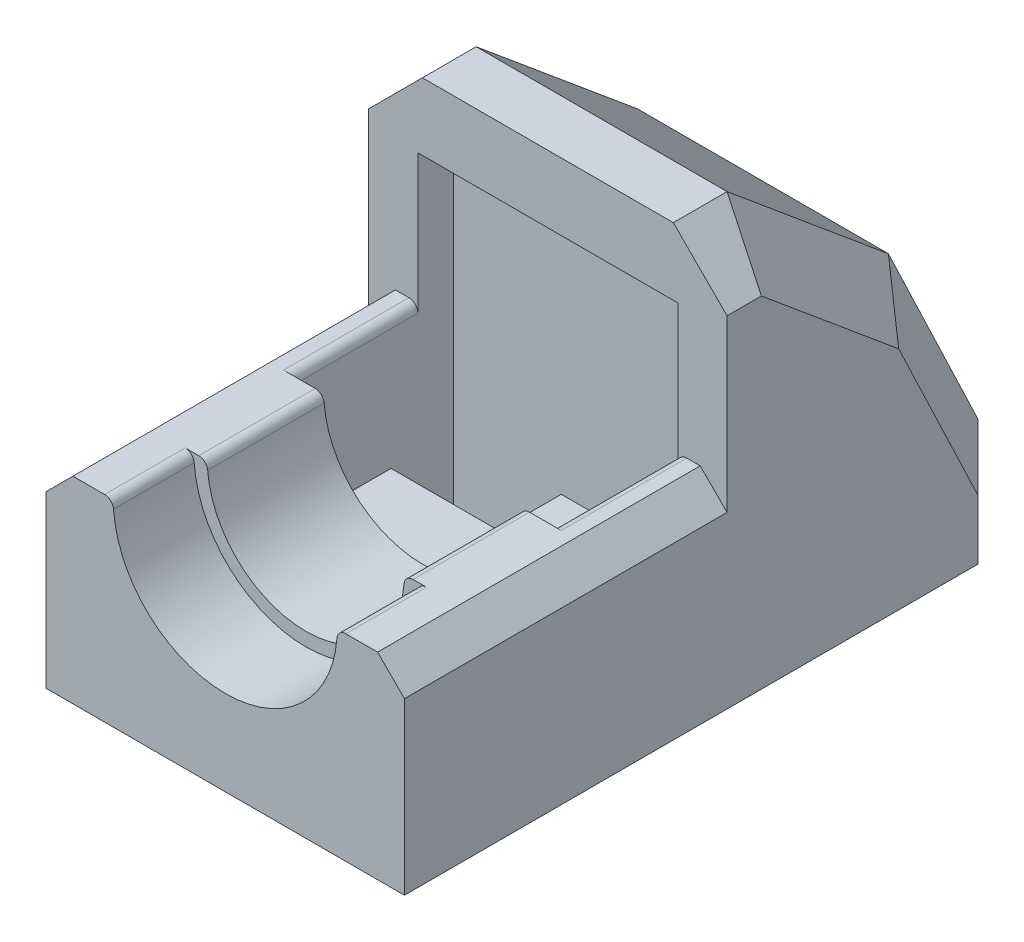
SolidWorks part; units mm, degrees
ref_plane "Ebene vorne" through (0, 0, 0) normal (0, 0, 1) x (1, 0, 0)
ref_plane "Ebene oben" through (0, 0, 0) normal (0, 1, 0) x (1, 0, 0)
ref_plane "Ebene rechts" through (0, 0, 0) normal (1, 0, 0) x (0, 0, -1)
sketch "Skizze1" plane through (0, 0, 0) normal (0, 0, 1) x (1, 0, 0)
  line L1 (0, 0) -> (20, 0)
  line L2 (0, 0) -> (0, 22)
  line L3 (0, 22) -> (20, 22)
  line L4 (20, 0) -> (20, 22)
  dimension "D1" = 22
  dimension "D2" = 20
extrude "Aufsatz-Linear austragen1" add sketch "Skizze1" along normal blind 35
sketch "Skizze2" plane through (0, 0, 35) normal (0, 0, 1) x (1, 0, 0)
  line L0 (0, 22) -> (0, 0) construction
  line L1 (20, 22) -> (0, 22) construction
  circle A0 centre (10, 11) radius 5.5
  dimension "D3" = 11
  dimension "D1" = 10
  dimension "D2" = 11
extrude "Schnitt-Linear austragen1" cut sketch "Skizze2" against normal blind 11
sketch "Skizze3" plane through (0, 0, 35) normal (0, 0, 1) x (1, 0, 0)
  line L0 (20, 0) -> (20, 22) construction
  line L1 (20, 22) -> (0, 22) construction
  circle A0 centre (10, 11) radius 6.25
  dimension "D1" = 10
  dimension "D2" = 11
extrude "Schnitt-Linear austragen2" cut sketch "Skizze3" against normal blind 4.5
sketch "Skizze5" plane through (0, 0, 24) normal (0, 0, 1) x (1, 0, 0)
  line L0 (0, 22) -> (0, 0) construction
  line L1 (2.75, 3.75) -> (17.25, 3.75)
  line L2 (2.75, 3.75) -> (2.75, 18.25)
  line L3 (2.75, 18.25) -> (17.25, 18.25)
  line L4 (17.25, 3.75) -> (17.25, 18.25)
  line L6 (0, 0) -> (20, 0) construction
  dimension "D1" = 14.5
  dimension "D2" = 14.5
  dimension "D3" = 2.75
  dimension "D4" = 3.75
extrude "Schnitt-Linear austragen3" cut sketch "Skizze5" against normal blind 9
sketch "Skizze13" plane through (0, 0, 35) normal (0, 0, 1) x (1, 0, 0)
  line L0 (20, 0) -> (20, 22) construction
  line L1 (0, 22) -> (20, 22)
  line L2 (0, 22) -> (0, 11)
  line L3 (0, 11) -> (20, 11)
  line L4 (20, 22) -> (20, 11)
extrude "Schnitt-Linear austragen6" cut sketch "Skizze13" against normal blind 18
sketch "Skizze16" plane through (0, 0, 0) normal (-1, 0, 0) x (0, 0, 1)
  line L0 (14, 22) -> (5, 14.5)
  line L1 (17, 22) -> (0, 22) construction
  line L2 (5, 14.5) -> (0, 4)
  line L3 (0, 22) -> (0, 0) construction
  line L4 (0, 4) -> (0, 22)
  line L5 (0, 22) -> (14, 22)
  line L6 (17, 22) -> (17, 11) construction
  dimension "D1" = 3
  dimension "D2" = 5
  dimension "D3" = 18
  dimension "D4" = 10.5
extrude "Schnitt-Linear austragen7" cut sketch "Skizze16" against normal through all
fillet "Verrundung1" radius 0.5 6 edges at (16.25, 11, 32.75) (3.75, 11, 32.75) (4.5, 11, 27.25) (15.5, 11, 27.25) (17.25, 11, 20.5) (2.75, 11, 20.5)
chamfer "Fase1" distance 3 angle 45 2 edges at (20, 22, 15.5) (0, 22, 15.5)
chamfer "Fase2" distance 3 angle 45 2 edges at (0, 16.75, 7.7) (20, 16.75, 7.7)
chamfer "Fase3" distance 3 angle 45 4 edges at (20, 6.0129, 0.9585) (20, 2, 0) (0, 6.0129, 0.9585) (0, 2, 0)
chamfer "Fase4" distance 1.5 angle 45 2 edges at (20, 11, 26) (0, 11, 26)
sketch "Skizze17" plane through (0, 3.75, 0) normal (0, 1, 0) x (1, 0, 0)
  line L1 (2.75, -15) -> (8.75, -15)
  line L2 (2.75, -15) -> (2.75, -18.5)
  line L3 (2.75, -18.5) -> (8.75, -18.5)
  line L4 (8.75, -15) -> (8.75, -18.5)
  dimension "D1" = 6
  dimension "D2" = 3.5
extrude "Schnitt-Linear austragen8" cut sketch "Skizze17" against normal through all
